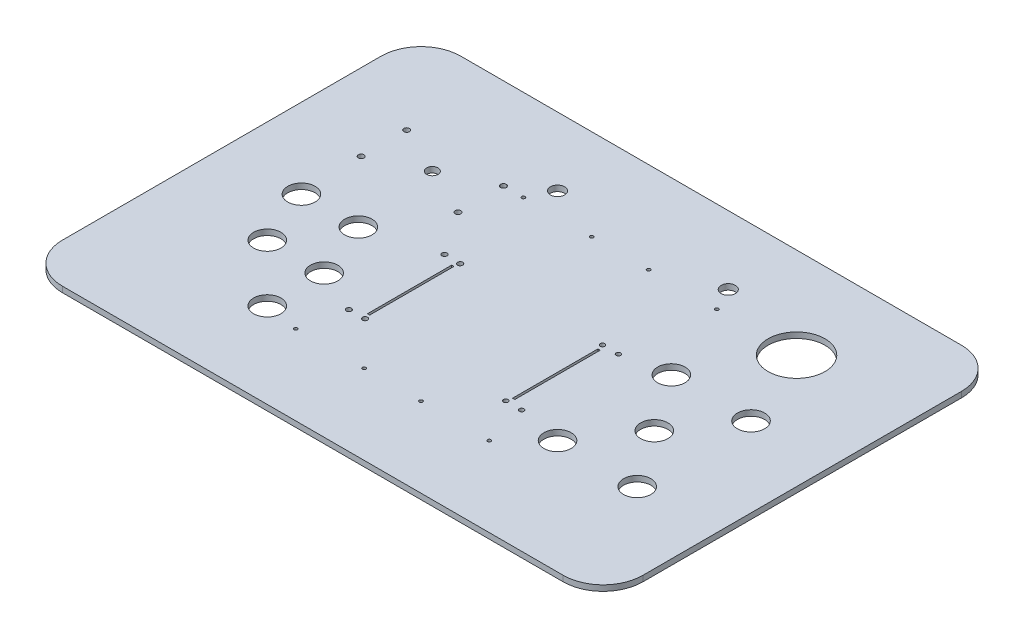
SolidWorks part; units mm, degrees
material "Perspex (TM) GS Acrylic Cast Sheet"
ref_plane "Front Plane" through (0, 0, 0) normal (0, 0, 1) x (1, 0, 0)
ref_plane "Top Plane" through (0, 0, 0) normal (0, 1, 0) x (1, 0, 0)
ref_plane "Right Plane" through (0, 0, 0) normal (1, 0, 0) x (0, 0, -1)
sketch "Sketch1" plane through (0, 0, 0) normal (0, 1, 0) x (1, 0, 0)
  line L1 (0, 0) -> (510, 0)
  line L2 (0, 0) -> (0, 350)
  line L3 (0, 350) -> (510, 350)
  line L4 (510, 0) -> (510, 350)
  dimension "D1" = 510
  dimension "D2" = 350
extrude "Boss-Extrude1" add sketch "Sketch1" along normal blind 5
sketch "Sketch2" plane through (0, 5, 0) normal (0, 1, 0) x (1, 0, 0)
  line L0 (510, 350) -> (0, 350) construction
  line L1 (110, 250) -> (175.8433, 250) construction
  line L2 (110, 250) -> (110, 296.2555) construction
  line L3 (0, 350) -> (0, 0) construction
  circle A0 centre (110, 250) radius 5
  circle A2 centre (152.5, 270) radius 2.5
  circle A3 centre (152.5, 230) radius 2.5
  circle A4 centre (67.5, 230) radius 2.5
  circle A5 centre (67.5, 270) radius 2.5
  dimension "D1" = 10
  dimension "D2" = 100
  dimension "D5" = 5
  dimension "D3" = 42.5
  dimension "D4" = 20
  dimension "D6" = 110
extrude "1 Joyystick" cut sketch "Sketch2" against normal through all
sketch "Sketch3" plane through (0, 5, 0) normal (0, 1, 0) x (1, 0, 0)
  line L0 (0, 350) -> (0, 0) construction
  line L2 (475, 350) -> (35, 350) construction
  circle A0 centre (70, 175) radius 12
  circle A1 centre (120, 175) radius 12
  circle A2 centre (90, 125) radius 12
  circle A3 centre (140, 125) radius 12
  circle A4 centre (140, 75) radius 12
  point P14 (120, 175)
  dimension "D1" = 24
  dimension "D2" = 24
  dimension "D3" = 24
  dimension "D4" = 24
  dimension "D5" = 24
  dimension "D11" = 175
  dimension "D6" = 70
  dimension "D7" = 50
  dimension "D8" = 50
  dimension "D9" = 50
  dimension "D10" = 50
  dimension "D12" = 20
extrude "1 Buttons" cut sketch "Sketch3" against normal through all
sketch "Sketch4" plane through (0, 5, 0) normal (0, 1, 0) x (1, 0, 0)
  line L0 (510, 350) -> (0, 350) construction
  line L1 (0, 350) -> (0, 0) construction
  circle A0 centre (180, 290) radius 6.25
  dimension "D1" = 12.5
  dimension "D2" = 60
  dimension "D3" = 180
extrude "1 Rocket Switch" cut sketch "Sketch4" against normal through all
sketch "Sketch5" plane through (0, 5, 0) normal (0, 1, 0) x (1, 0, 0)
  line L0 (192, 150) -> (210.2533, 150) construction
  line L1 (190, 187) -> (192, 187)
  line L2 (190, 187) -> (190, 113)
  line L3 (190, 113) -> (192, 113)
  line L4 (192, 187) -> (192, 113)
  line L5 (190, 150) -> (192, 150) construction
  line L7 (510, 350) -> (0, 350) construction
  line L8 (185.7526, 194.2625) -> (184.4144, 100.0138) construction
  line L9 (0, 350) -> (0, 0) construction
  circle A0 centre (178.7197, 192) radius 2.25
  circle A1 centre (192.7183, 191.8012) radius 2.25
  circle A2 centre (192.7183, 108.1988) radius 2.25
  circle A3 centre (178.7197, 108) radius 2.25
  point P7 (191, 187)
  dimension "D5" = 4.5
  dimension "D1" = 2
  dimension "D2" = 74
  dimension "D3" = 5.35
  dimension "D4" = 190
  dimension "D6" = 7
  dimension "D7" = 200
  dimension "D8" = 5
extrude "1 Potentiometer" cut sketch "Sketch5" against normal through all
fillet "Fillet1" radius 35 4 edges at (0, 2.5, 0) (510, 2.5, 0) (510, 2.5, -350) (0, 2.5, -350)
sketch "Sketch6" plane through (0, 5, 0) normal (0, 1, 0) x (1, 0, 0)
  line L0 (510, 35) -> (510, 315) construction
  line L1 (475, 350) -> (35, 350) construction
  circle A0 centre (440, 200) radius 12
  circle A1 centre (370, 200) radius 12
  circle A2 centre (440, 100) radius 12
  circle A3 centre (370, 100) radius 12
  circle A4 centre (405, 150) radius 12
  point P12 (380, 148.1839)
  point P13 (0, 0)
  point P16 (0, 0)
  dimension "D1" = 24
  dimension "D2" = 24
  dimension "D3" = 24
  dimension "D4" = 24
  dimension "D5" = 24
  dimension "D6" = 70
  dimension "D7" = 70
  dimension "D8" = 70
  dimension "D9" = 100
  dimension "D10" = 50
  dimension "D11" = 150
  dimension "D12" = 35
extrude "2 Buttons" cut sketch "Sketch6" against normal through all
sketch "Sketch8" plane through (0, 5, 0) normal (0, 1, 0) x (1, 0, 0)
  line L0 (319, 187.5) -> (319, 112.5) construction
  line L1 (320, 187.5) -> (318, 187.5)
  line L2 (320, 187.5) -> (320, 112.5)
  line L3 (320, 112.5) -> (318, 112.5)
  line L4 (318, 187.5) -> (318, 112.5)
  line L5 (324, 205.9826) -> (324, 86.9169) construction
  line L6 (320, 150) -> (327.2352, 150) construction
  line L8 (510, 35) -> (510, 315) construction
  line L9 (475, 350) -> (35, 350) construction
  circle A0 centre (331, 192.5) radius 2
  circle A1 centre (331, 107.5) radius 2
  circle A2 centre (317, 107.5) radius 2
  circle A3 centre (317, 192.5) radius 2
  point P22 (319, 150)
  dimension "D2" = 4
  dimension "D3" = 42.5
  dimension "D1" = 5
  dimension "D4" = 1
  dimension "D5" = 2
  dimension "D6" = 190
  dimension "D7" = 200
  dimension "D8" = 7
sketch "Sketch9" plane through (0, 5, 0) normal (0, 1, 0) x (1, 0, 0)
  line L0 (510, 35) -> (510, 315) construction
  line L1 (475, 350) -> (35, 350) construction
  circle A0 centre (410, 270) radius 25
  dimension "D1" = 50
  dimension "D2" = 100
  dimension "D3" = 80
extrude "2 speaker" cut sketch "Sketch9" against normal through all
sketch "Sketch10" plane through (0, 5, 0) normal (0, 1, 0) x (1, 0, 0)
  line L1 (510, 35) -> (510, 315) construction
  line L2 (475, 350) -> (35, 350) construction
  circle A0 centre (330, 290) radius 6.25
  dimension "D1" = 12.5
  dimension "D2" = 60
  dimension "D3" = 180
extrude "2 Rocket Switch" cut sketch "Sketch10" against normal through all
extrude "2 Potentiometer" cut sketch "Sketch8" against normal through all
sketch "Sketch11" plane through (0, 5, 0) normal (0, 1, 0) x (1, 0, 0)
  line L0 (280, 70) -> (280, 268.5) construction
  line L1 (340, 70) -> (340, 270) construction
  line L2 (365.4787, 70) -> (281.3845, 70) construction
  line L3 (356.6021, 270) -> (280, 270) construction
  line L4 (510, 35) -> (510, 315) construction
  line L5 (475, 350) -> (35, 350) construction
  circle A0 centre (340, 70) radius 1.5
  circle A1 centre (280, 70) radius 1.5
  circle A2 centre (280, 270) radius 1.5
  circle A3 centre (340, 270) radius 1.5
  dimension "D1" = 200
  dimension "D3" = 3
  dimension "D4" = 3
  dimension "D5" = 3
  dimension "D6" = 3
  dimension "D2" = 60
  dimension "D7" = 170
  dimension "D8" = 80
extrude "2 PCB1" cut sketch "Sketch11" against normal through all
sketch "Sketch12" plane through (0, 5, 0) normal (0, 1, 0) x (1, 0, 0)
  line L0 (159.4963, 70) -> (271.8437, 70) construction
  line L1 (244.3419, 270) -> (170, 270) construction
  line L2 (230, 70) -> (230, 270) construction
  line L3 (170, 30.2464) -> (170, 266.6202) construction
  line L5 (475, 350) -> (35, 350) construction
  line L6 (0, 315) -> (0, 35) construction
  circle A0 centre (230, 70) radius 1.5
  circle A1 centre (170, 70) radius 1.5
  circle A2 centre (230, 270) radius 1.5
  circle A3 centre (170, 270) radius 1.5
  point P4 (220, 268.5)
  point P5 (158.2329, 270)
  dimension "D3" = 3
  dimension "D4" = 3
  dimension "D7" = 3
  dimension "D8" = 3
  dimension "D1" = 200
  dimension "D2" = 60
  dimension "D5" = 170
  dimension "D6" = 80
extrude "1 PCB2" cut sketch "Sketch12" against normal through all
